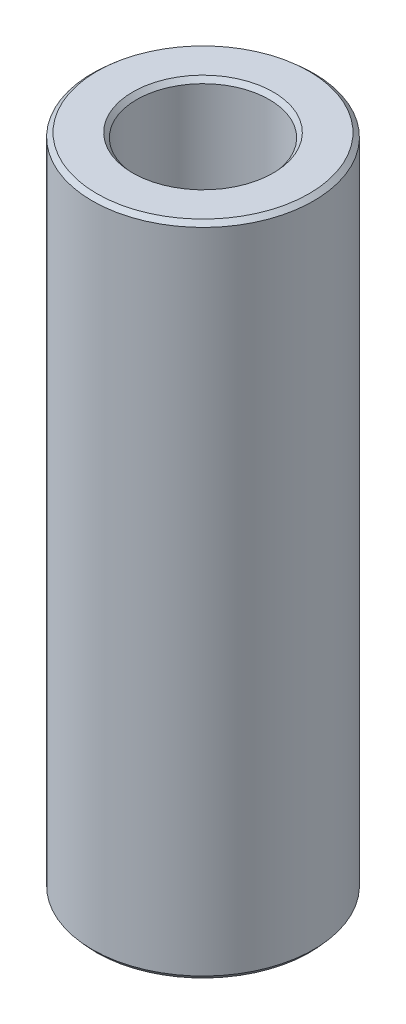
SolidWorks part; units mm, degrees
ref_plane "Front Plane" through (0, 0, 0) normal (0, 0, 1) x (1, 0, 0)
ref_plane "Top Plane" through (0, 0, 0) normal (0, 1, 0) x (1, 0, 0)
ref_plane "Right Plane" through (0, 0, 0) normal (1, 0, 0) x (0, 0, -1)
sketch "Sketch1" plane through (0, 0, 0) normal (0, 1, 0) x (1, 0, 0)
  circle A0 centre (0, 0) radius 37.5
  dimension "SLEEVE_OD" = 75
extrude "Boss-Extrude1" add sketch "Sketch1" along normal blind 222.6637
sketch "Sketch2" plane through (0, 0, 0) normal (0, 1, 0) x (1, 0, 0)
  circle A0 centre (0, 0) radius 22.4601
  dimension "BORE_D" = 44.9202
extrude "Cut-Extrude1" cut sketch "Sketch2" along normal through all
chamfer "Chamfer1" distance 1.3571 angle 48.705 4 edges at (0, 222.6637, 22.4601) (0, 0, 22.4601) (0, 0, 37.5) (0, 222.6637, 37.5) first distance on face at (0, 222.6637, 22.4601) first distance on face at (0, 0, 22.4601) first distance on face at (0, 222.6637, 37.5)
